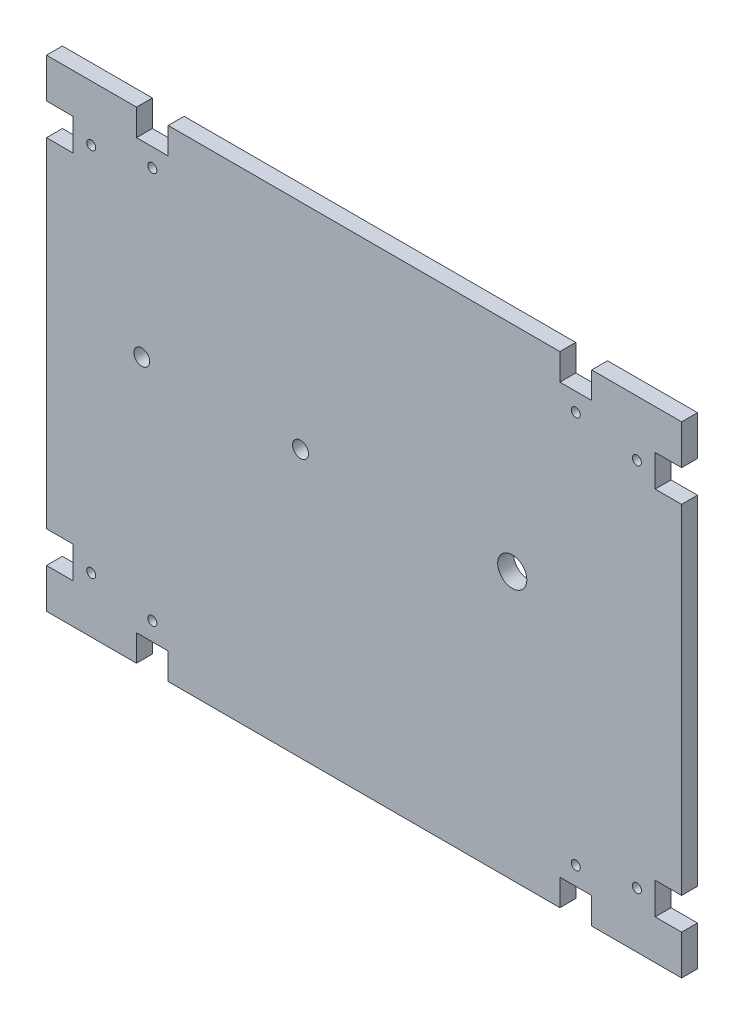
SolidWorks part; units mm, degrees
ref_plane "Front Plane" through (0, 0, 0) normal (0, 0, 1) x (1, 0, 0)
ref_plane "Top Plane" through (0, 0, 0) normal (0, 1, 0) x (1, 0, 0)
ref_plane "Right Plane" through (0, 0, 0) normal (1, 0, 0) x (0, 0, -1)
sketch "Sketch1" plane through (0, 0, 0) normal (0, 0, 1) x (1, 0, 0)
  line L1 (0, 0) -> (120, 0)
  line L2 (0, 0) -> (0, -91)
  line L3 (0, -91) -> (120, -91)
  line L4 (120, 0) -> (120, -91)
  dimension "D6" = 120
  dimension "D7" = 91
extrude "Boss-Extrude1" add sketch "Sketch1" along normal blind 3 contours L2 L3 L4 L1 region at (60, -45.5, 0)
sketch "Sketch2" plane through (0, 0, 3) normal (0, 0, 1) x (1, 0, 0)
  line L12 (0, 0) -> (0, -91) construction
  line L14 (0, 0) -> (120, 0) construction
  line L15 (0, -40.5) -> (120, -40.5) construction
  circle A28 centre (18, -40.4) radius 1.5
  circle A37 centre (48, -40.5) radius 1.5
  circle A38 centre (88, -40.5) radius 2.75
  dimension "D4" = 0.1
  dimension "D5" = 5.5
  dimension "D1" = 3
  dimension "D2" = 40
  dimension "D6" = 3
  dimension "D3" = 18
  dimension "D7" = 30
  dimension "D8" = 40.5
extrude "Cut-Extrude1" cut sketch "Sketch2" against normal up to surface (3 mm away) up to face at (60, -45.5, 0)
sketch "Sketch3" plane through (0, 0, 3) normal (0, 0, 1) x (1, 0, 0)
  line L1 (0, 0) -> (0, -91) construction
  line L2 (15, -75.4) -> (35, -75.4) construction
  line L3 (15, -74.05) -> (35, -74.05)
  line L4 (15, -76.75) -> (35, -76.75)
  arc A1 (15, -74.05) -> (15, -76.75) centre (15, -75.4) ccw
  arc A2 (35, -76.75) -> (35, -74.05) centre (35, -75.4) ccw
  circle A3 centre (18, -40.4) radius 1.5 construction
  point P7 (25, -75.4)
  dimension "D3" = 2.7
  dimension "D1" = 35
  dimension "D2" = 15
  dimension "D4" = 20
extrude "Cut-Extrude3" [suppressed] cut sketch "Sketch3" against normal through all
sketch "Sketch4" plane through (0, 0, 0) normal (-1, 0, 0) x (0, 0, 1)
  line L0 (0, -45.5) -> (3, -45.5)
  line L1 (0, 0) -> (0, -91) construction
  line L2 (3, 0) -> (3, -91) construction
  line L3 (1.5, -10.5) -> (1.5, -80.5)
  circle A0 centre (1.5, -80.5) radius 0.85
  circle A1 centre (1.5, -10.5) radius 0.85
  point P9 (1.5, -45.5)
  dimension "D2" = 1.7
  dimension "D1" = 70
extrude "Cut-Extrude4" [suppressed] cut sketch "Sketch4" against normal blind 10 contours A1 | A0
sketch "Sketch5" plane through (0, 0, 3) normal (0, 0, 1) x (1, 0, 0)
  line L0 (0, 0) -> (0, -91) construction
  line L1 (0, -10.5) -> (8.45, -10.5) construction
  line L2 (0, -7.5) -> (5, -7.5)
  line L3 (0, -7.5) -> (0, -13.5)
  line L4 (0, -13.5) -> (5, -13.5)
  line L5 (5, -7.5) -> (5, -13.5)
  line L6 (0, 0) -> (120, 0) construction
  line L7 (60, 0) -> (60, -91) construction
  line L8 (0, -91) -> (120, -91) construction
  line L9 (0, -45.5) -> (120, -45.5) construction
  line L10 (120, 0) -> (120, -91) construction
  line L11 (20, -2.5) -> (20, -8.45) construction
  line L12 (17, 0) -> (23, 0)
  line L13 (17, 0) -> (17, -5)
  line L14 (17, -5) -> (23, -5)
  line L15 (23, 0) -> (23, -5)
  line L16 (17, 0) -> (23, -5) construction
  line L17 (0, -80.5) -> (8.45, -80.5) construction
  line L18 (0, -77.5) -> (5, -77.5)
  line L19 (0, -83.5) -> (5, -83.5)
  line L20 (17, -5) -> (23, 0) construction
  line L21 (17, -86) -> (23, -91) construction
  line L22 (17, -91) -> (23, -86) construction
  line L23 (20, -88.5) -> (20, -82.55) construction
  line L24 (5, -83.5) -> (5, -77.5)
  line L25 (23, -91) -> (23, -86)
  line L26 (0, -83.5) -> (0, -77.5)
  line L27 (17, -86) -> (23, -86)
  line L28 (120, -80.5) -> (111.55, -80.5) construction
  line L29 (120, -10.5) -> (111.55, -10.5) construction
  line L30 (120, -83.5) -> (115, -83.5)
  line L31 (120, -83.5) -> (120, -77.5)
  line L32 (120, -77.5) -> (115, -77.5)
  line L33 (115, -83.5) -> (115, -77.5)
  line L34 (17, -91) -> (17, -86)
  line L35 (17, -91) -> (23, -91)
  line L36 (100, -88.5) -> (100, -82.55) construction
  line L37 (103, -91) -> (97, -86) construction
  line L38 (103, -86) -> (97, -91) construction
  line L39 (103, -5) -> (97, 0) construction
  line L40 (120, -13.5) -> (115, -13.5)
  line L41 (120, -7.5) -> (115, -7.5)
  line L42 (103, 0) -> (97, -5) construction
  line L43 (100, -2.5) -> (100, -8.45) construction
  line L44 (103, -91) -> (97, -91)
  line L45 (103, -91) -> (103, -86)
  line L46 (115, -7.5) -> (115, -13.5)
  line L47 (103, -86) -> (97, -86)
  line L48 (120, -7.5) -> (120, -13.5)
  line L49 (97, -91) -> (97, -86)
  line L50 (97, 0) -> (97, -5)
  line L51 (103, -5) -> (97, -5)
  line L52 (103, 0) -> (103, -5)
  line L53 (103, 0) -> (97, 0)
  circle A0 centre (8.45, -10.5) radius 0.85
  circle A1 centre (8.45, -80.5) radius 0.85
  circle A2 centre (111.55, -80.5) radius 0.85
  circle A3 centre (111.55, -10.5) radius 0.85
  circle A4 centre (20, -8.45) radius 0.85
  circle A5 centre (20, -82.55) radius 0.85
  circle A6 centre (100, -82.55) radius 0.85
  circle A7 centre (100, -8.45) radius 0.85
  point P43 (20, -2.5)
  point P55 (20, -88.5)
  point P70 (100, -88.5)
  point P71 (100, -2.5)
  dimension "D1" = 1.7
  dimension "D7" = 1.7
  dimension "D2" = 8.45
  dimension "D3" = 5
  dimension "D4" = 6
  dimension "D5" = 5
  dimension "D6" = 6
  dimension "D8" = 0
  dimension "D9" = 8.45
  dimension "D10" = 80
  dimension "D11" = 70
extrude "Cut-Extrude5" cut sketch "Sketch5" against normal through all
